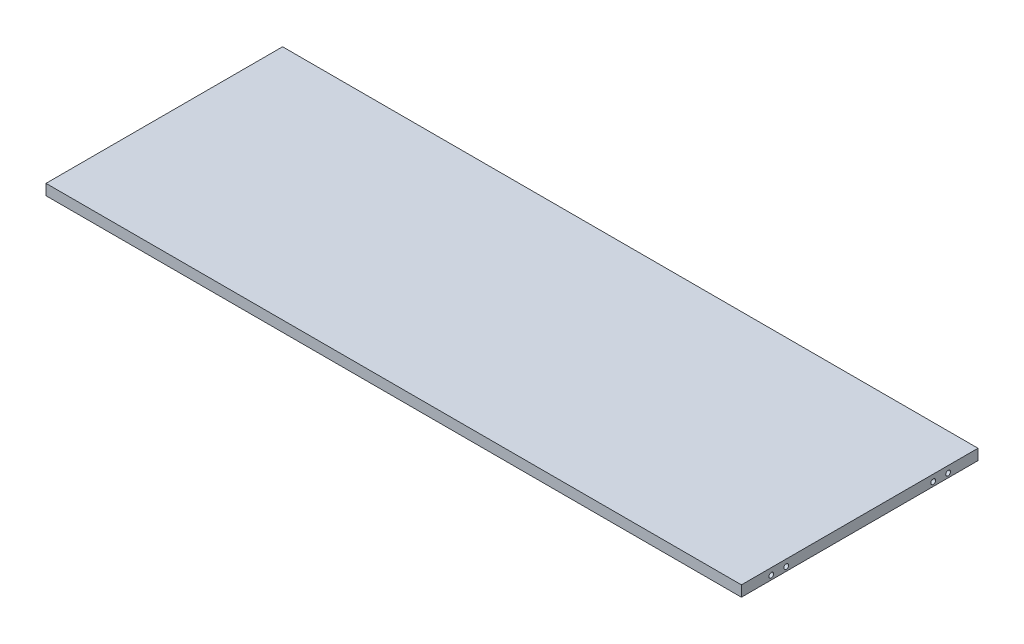
SolidWorks part; units mm, degrees
ref_plane "Front Plane" through (0, 0, 0) normal (0, 0, 1) x (1, 0, 0)
ref_plane "Top Plane" through (0, 0, 0) normal (0, 1, 0) x (1, 0, 0)
ref_plane "Right Plane" through (0, 0, 0) normal (1, 0, 0) x (0, 0, -1)
ref_plane "Back Plane" through (0, 0, -396) normal (0, 0, 1) x (1, 0, 0)
ref_plane "Bottom Plane" through (0, -18, 0) normal (0, 1, 0) x (-1, 0, 0)
ref_plane "Left Plane" through (-1164, 0, 0) normal (1, 0, 0) x (0, 0, -1)
sketch "Sketch1" plane through (0, -18, 0) normal (0, 1, 0) x (-1, 0, 0)
  line L0 (1164, 55) -> (1164, -55) construction
  line L1 (1164, -396) -> (0, -396)
  line L2 (1164, -396) -> (1164, 0)
  line L3 (1164, 0) -> (0, 0)
  line L4 (0, -396) -> (0, 0)
  line L5 (55, -396) -> (-55, -396) construction
  line L7 (0, 55) -> (0, -55) construction
  line L8 (55, 0) -> (-55, 0) construction
extrude "Base Panel" add sketch "Sketch1" along normal up to surface (18 mm away) up to plane "Top Plane"
sketch "Sketch2" plane through (-1164, 0, 0) normal (1, 0, 0) x (0, 0, -1)
  circle A0 centre (50, -11) radius 4
  circle A1 centre (75, -11) radius 4
  circle A2 centre (321, -11) radius 4
  circle A3 centre (346, -11) radius 4
  dimension "D5" = 8
  dimension "D6" = 8
  dimension "D1" = 50
  dimension "D2" = 75
  dimension "D3" = 50
  dimension "D4" = 75
  dimension "D7" = 11
extrude "Extrude2" cut sketch "Sketch2" along normal blind 15
sketch "Sketch3" plane through (0, 0, 0) normal (1, 0, 0) x (0, 0, -1)
  circle A0 centre (346, -11) radius 4 construction
  circle A1 centre (321, -11) radius 4 construction
  circle A2 centre (75, -11) radius 4 construction
  circle A3 centre (50, -11) radius 4 construction
  circle A4 centre (346, -11) radius 4
  circle A5 centre (321, -11) radius 4
  circle A6 centre (75, -11) radius 4
  circle A7 centre (50, -11) radius 4
extrude "Extrude3" cut sketch "Sketch3" against normal blind 15
sketch "Sketch4" plane through (0, 0, 0) normal (0, 1, 0) x (1, 0, 0)
  line L0 (-1164, 0) -> (0, 0) construction
  line L1 (-582, 15) -> (0, 15) construction
  line L2 (0, 0) -> (0, 396) construction
  line L3 (-582, 15) -> (-1164, 15) construction
  line L4 (-1164, 396) -> (-1164, 0) construction
  circle A0 centre (-582, 15) radius 4
  circle A1 centre (-582, 60) radius 4
  dimension "D3" = 8
  dimension "D1" = 15
  dimension "D2" = 45
extrude "Extrude4" [suppressed] cut sketch "Sketch4" against normal blind 10
sketch "Sketch5" plane through (0, -18, 0) normal (0, 1, 0) x (-1, 0, 0)
  circle A0 centre (25, -50) radius 15
  circle A1 centre (25, -346) radius 15
  circle A2 centre (1139, -50) radius 15
  circle A3 centre (1139, -346) radius 15
  dimension "D5" = 30
  dimension "D1" = 25
  dimension "D2" = 25
  dimension "D3" = 50
  dimension "D4" = 50
extrude "Extrude17" cut sketch "Sketch5" along normal blind 13
extrude "Taglio-Estrusione1" cut sketch "Sketch4<2>" along normal blind 10 from surface starting at face at (-1139, -18, -35)
sketch "Sketch4<2>" plane through (0, 0, 0) normal (0, 1, 0) x (1, 0, 0) same geometry as "Sketch4"
